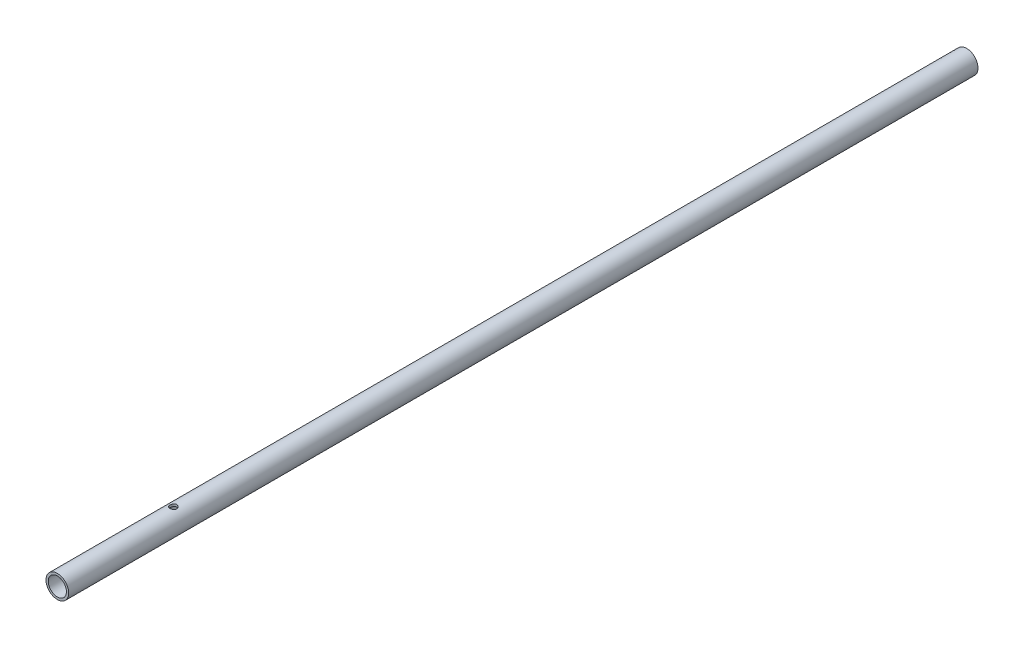
SolidWorks part; units mm, degrees
material "Thornel Mat VMA"
ref_plane "前视基准面" through (0, 0, 0) normal (0, 0, 1) x (1, 0, 0)
ref_plane "上视基准面" through (0, 0, 0) normal (0, 1, 0) x (1, 0, 0)
ref_plane "右视基准面" through (0, 0, 0) normal (1, 0, 0) x (0, 0, -1)
other "Configuration Table"
sketch "草图1" plane through (0, 0, 0) normal (0, 0, 1) x (1, 0, 0)
  circle A0 centre (0, 0) radius 5
  circle A1 centre (0, 0) radius 4
  dimension "D1" = 10
  dimension "D2" = 1
extrude "凸台-拉伸1" add sketch "草图1" along normal blind 400
sketch "草图2" plane through (0, 0, 0) normal (0, 1, 0) x (1, 0, 0)
  circle A0 centre (0, -31.3344) radius 1.5
  dimension "D1" = 3
  dimension "D2" = 31.3344
extrude "切除-拉伸1" cut sketch "草图2" against normal through all
sketch "草图3" plane through (0, 0, 0) normal (0, 1, 0) x (1, 0, 0)
  line L0 (7, -345) -> (-7, -345) construction
  circle A1 centre (0, -349) radius 1.5
  point P4 (0, 0)
  dimension "D1" = 3
  dimension "D2" = 4
extrude "切除-拉伸2" cut sketch "草图3" along normal through all contours A1
